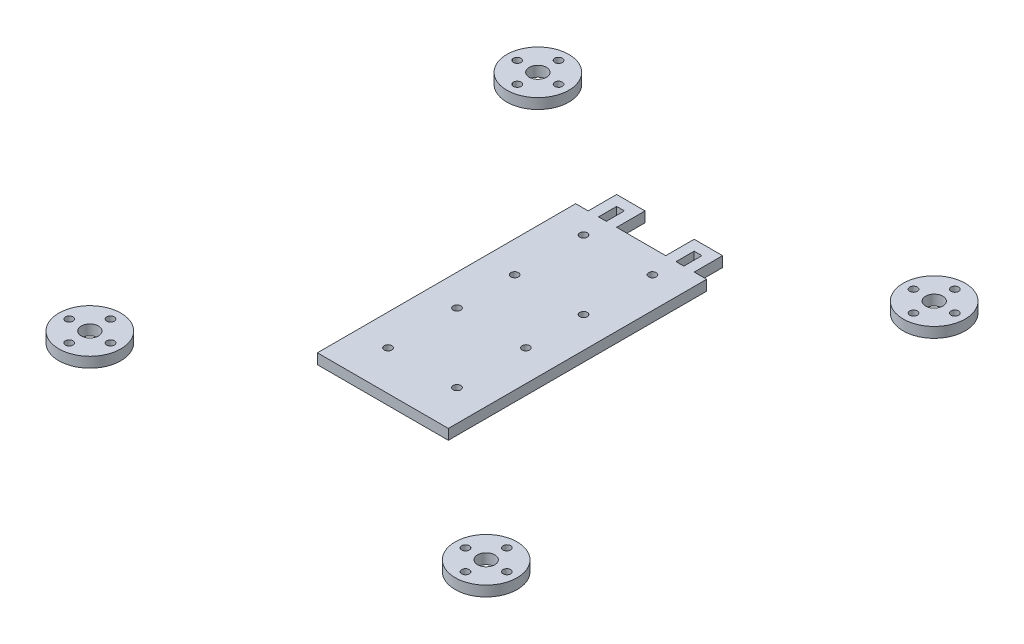
SolidWorks part; units mm, degrees
ref_plane "Front Plane" through (0, 0, 0) normal (0, 0, 1) x (1, 0, 0)
ref_plane "Top Plane" through (0, 0, 0) normal (0, 1, 0) x (1, 0, 0)
ref_plane "Right Plane" through (0, 0, 0) normal (1, 0, 0) x (0, 0, -1)
sketch "Sketch1" plane through (0, 0, 0) normal (0, 1, 0) x (1, 0, 0)
  line L0 (0, 37.475) -> (0, -37.475) construction
  line L1 (19, 37.475) -> (-19, 37.475)
  line L2 (19, 37.475) -> (19, -37.475)
  line L3 (19, -37.475) -> (-19, -37.475)
  line L4 (-19, 37.475) -> (-19, -37.475)
  line L5 (19, 37.475) -> (-19, -37.475) construction
  line L6 (19, -37.475) -> (-19, 37.475) construction
  line L8 (57.5, -65) -> (-57.5, -65)
  line L9 (57.5, -65) -> (57.5, 65)
  line L10 (57.5, 65) -> (-57.5, 65)
  line L11 (-57.5, -65) -> (-57.5, 65)
  line L12 (57.5, -65) -> (-57.5, 65) construction
  line L13 (57.5, 65) -> (-57.5, -65) construction
  line L17 (-11.25, 45.725) -> (-11.25, 37.475) construction
  line L18 (-7.125, 37.475) -> (-15.375, 37.475)
  line L19 (-57.5, 65) -> (0, 37.475) construction
  line L20 (-10, 30.75) -> (10, 30.75)
  line L21 (-10, 30.75) -> (-10, 10.75)
  line L22 (-10, 10.75) -> (10, 10.75)
  line L23 (10, 30.75) -> (10, 10.75)
  line L24 (-10, 30.75) -> (10, 10.75) construction
  line L25 (-10, 10.75) -> (10, 30.75) construction
  line L26 (-14.5, 5.525) -> (14.5, 5.525)
  line L27 (-14.5, 5.525) -> (-14.5, 35.975)
  line L28 (-14.5, 35.975) -> (14.5, 35.975)
  line L29 (14.5, 5.525) -> (14.5, 35.975)
  line L30 (-14.5, 5.525) -> (14.5, 35.975) construction
  line L31 (-14.5, 35.975) -> (14.5, 5.525) construction
  line L32 (-10, -5.975) -> (10, -5.975)
  line L33 (-10, -5.975) -> (-10, -25.975)
  line L34 (-10, -25.975) -> (10, -25.975)
  line L35 (10, -5.975) -> (10, -25.975)
  line L36 (-10, -5.975) -> (10, -25.975) construction
  line L37 (-10, -25.975) -> (10, -5.975) construction
  line L38 (-15.75, -35.975) -> (15.75, -35.975)
  line L39 (-15.75, -35.975) -> (-15.75, 4.025)
  line L40 (-15.75, 4.025) -> (15.75, 4.025)
  line L41 (15.75, -35.975) -> (15.75, 4.025)
  line L42 (-15.75, -35.975) -> (15.75, 4.025) construction
  line L43 (-15.75, 4.025) -> (15.75, -35.975) construction
  line L48 (-7.125, 37.475) -> (-7.125, 45.725)
  line L49 (-7.125, 45.725) -> (-15.375, 45.725)
  line L58 (-57.5, 0) -> (57.5, 0) construction
  line L59 (-15.375, 37.475) -> (-15.375, 45.725)
  line L63 (-12.375, 42.725) -> (-10.125, 42.725)
  line L64 (-12.375, 42.725) -> (-12.375, 37.475)
  line L65 (-12.375, 37.475) -> (-10.125, 37.475)
  line L66 (-10.125, 42.725) -> (-10.125, 37.475)
  line L67 (-12.375, 42.725) -> (-10.125, 37.475) construction
  line L68 (-12.375, 37.475) -> (-10.125, 42.725) construction
  line L69 (-12.375, 42.725) -> (-15.375, 42.725) construction
  line L71 (-12.375, 42.725) -> (-12.375, 45.725) construction
  line L74 (7.125, 37.475) -> (15.375, 37.475)
  line L75 (15.375, 37.475) -> (15.375, 45.725)
  line L76 (7.125, 45.725) -> (15.375, 45.725)
  line L77 (7.125, 37.475) -> (7.125, 45.725)
  line L78 (12.375, 42.725) -> (10.125, 42.725)
  line L79 (12.375, 42.725) -> (12.375, 37.475)
  line L80 (12.375, 37.475) -> (10.125, 37.475)
  line L81 (10.125, 42.725) -> (10.125, 37.475)
  circle A0 centre (-57.5, 65) radius 36
  circle A1 centre (-57.5, 65) radius 6
  circle A2 centre (-57.5, 65) radius 9
  circle A3 centre (-10, 30.75) radius 1.1
  circle A4 centre (10, 30.75) radius 1.1
  circle A5 centre (10, 10.75) radius 1.1
  circle A6 centre (-10, 10.75) radius 1.1
  circle A7 centre (-10, -5.975) radius 1.1
  circle A8 centre (10, -5.975) radius 1.1
  circle A9 centre (10, -25.975) radius 1.1
  circle A10 centre (-10, -25.975) radius 1.1
  circle A11 centre (-57.5, 71) radius 1.1
  circle A12 centre (-63.5, 65) radius 1.1
  circle A13 centre (-57.5, 59) radius 1.1
  circle A14 centre (-51.5, 65) radius 1.1
  circle A15 centre (57.5, 59) radius 1.1
  circle A16 centre (51.5, 65) radius 1.1
  circle A17 centre (57.5, 71) radius 1.1
  circle A18 centre (63.5, 65) radius 1.1
  circle A19 centre (57.5, 65) radius 9
  circle A20 centre (57.5, -65) radius 9
  circle A21 centre (51.5, -65) radius 1.1
  circle A22 centre (57.5, -59) radius 1.1
  circle A23 centre (63.5, -65) radius 1.1
  circle A24 centre (57.5, -71) radius 1.1
  circle A25 centre (-57.5, -59) radius 1.1
  circle A26 centre (-51.5, -65) radius 1.1
  circle A27 centre (-57.5, -71) radius 1.1
  circle A28 centre (-63.5, -65) radius 1.1
  circle A29 centre (-57.5, -65) radius 9
  circle A30 centre (-57.5, -65) radius 36
  circle A31 centre (57.5, 65) radius 36
  circle A32 centre (57.5, -65) radius 36
  circle A33 centre (-57.5, 65) radius 2.5
  circle A34 centre (57.5, 65) radius 2.5
  circle A35 centre (57.5, -65) radius 2.5
  circle A36 centre (-57.5, -65) radius 2.5
  point P0 (0, 0)
  point P8 (0, 0)
  point P16 (0, 20.75)
  point P26 (0, 20.75)
  point P31 (0, -15.975)
  point P36 (0, -15.975)
  point P61 (-11.25, 40.1)
  dimension "D3" = 72
  dimension "D4" = 12
  dimension "D5" = 3
  dimension "D17" = 2.2
  dimension "D19" = 5
  dimension "D2" = 1.5
  dimension "D6" = 115
  dimension "D7" = 130
  dimension "D8" = 3.25
  dimension "D9" = 22.5
  dimension "D10" = 20
  dimension "D11" = 29
  dimension "D12" = 30.45
  dimension "D13" = 40
  dimension "D14" = 31.5
  dimension "D15" = 1.5
  dimension "D16" = 1.5
  dimension "D18" = 2.25
  dimension "D20" = 5.25
  dimension "D21" = 3
extrude "Boss-Extrude1" add sketch "Sketch1" along normal blind 3 contours L63 L66 L1 L48 L49 L59 L18 L64 | L81 L78 L79 L1 L75 L76 L77 | A2 | A11 | A14 | A13 | A12 | A19 | A15 | A18 | A17 | A16 | L1 L4 L3 L2 | A29 | A27 | A28 | A25 | A26 | A20 | A24 | A21 | A22 | A23 | A4 | A3 | A7 | A8 | A9 | A10 | A5 | A6 | A33 | A34 | A35 | A36 region at (13.875, 0, -37.5917) region at (-15.2583, 0, -41.6)
